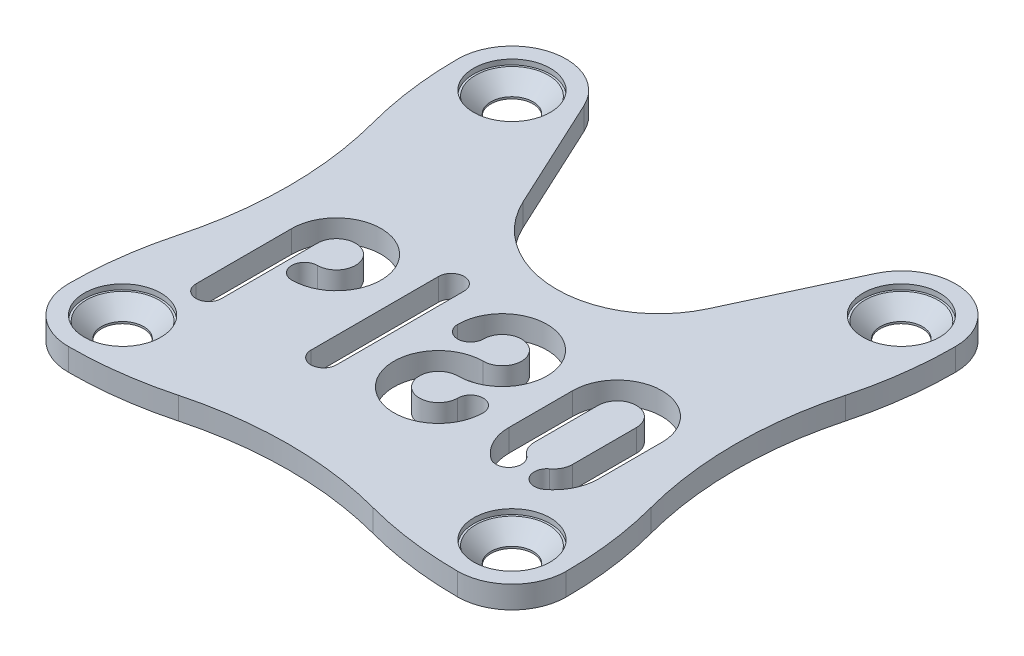
SolidWorks part; units mm, degrees
ref_plane "Front Plane" through (0, 0, 0) normal (0, 0, 1) x (1, 0, 0)
ref_plane "Top Plane" through (0, 0, 0) normal (0, 1, 0) x (1, 0, 0)
ref_plane "Right Plane" through (0, 0, 0) normal (1, 0, 0) x (0, 0, -1)
sketch "Sketch1" plane through (0, 0, 0) normal (0, 1, 0) x (1, 0, 0)
  line L0 (0, 19.5) -> (0, -19.5) construction
  line L1 (-19.5, 19.5) -> (19.5, 19.5)
  line L2 (-19.5, 19.5) -> (-19.5, -19.5)
  line L3 (-19.5, -19.5) -> (19.5, -19.5)
  line L4 (19.5, 19.5) -> (19.5, -19.5)
  line L5 (-19.5, 19.5) -> (19.5, -19.5) construction
  line L6 (-19.5, -19.5) -> (19.5, 19.5) construction
  line L7 (-19.5, 35.2) -> (-19.5, -19.5) construction
  circle A0 centre (-15.25, 15.25) radius 1.65
  circle A1 centre (15.25, 15.25) radius 1.65
  circle A2 centre (-15.25, -15.25) radius 1.65
  circle A3 centre (15.25, -15.25) radius 1.65
  circle A4 centre (15.25, 15.25) radius 1.65 construction
  circle A5 centre (15.25, -15.25) radius 1.65 construction
  circle A6 centre (-15.25, -15.25) radius 1.65 construction
  circle A7 centre (-15.25, 15.25) radius 1.65 construction
  point P0 (0, 0)
extrude "Shape" add sketch "Sketch1" along normal blind 1.75
sketch "Sketch2" plane through (0, 1.75, 0) normal (0, 1, 0) x (1, 0, 0)
  line L0 (0, 19.5) -> (0, -19.5) construction
  line L2 (-15.25, 16.9) -> (-15.25, -16.9) construction
  line L3 (-15.25, 0) -> (-19.5, 0) construction
  line L4 (-19.5, 19.5) -> (-19.5, -19.5) construction
  line L5 (19.5, 19.5) -> (-19.5, 19.5) construction
  line L6 (-19.5, -19.5) -> (19.5, -19.5) construction
  line L7 (-15.25, 0) -> (-11, 0) construction
  line L8 (-7.2551, 8.1291) -> (-12.5383, 19.5)
  line L9 (7.2551, 8.1291) -> (12.5383, 19.5)
  line L10 (-12.5383, 19.5) -> (12.5383, 19.5)
  line L14 (19.5, -19.5) -> (19.5, 19.5)
  line L15 (19.5, 19.5) -> (-19.5, 19.5)
  line L16 (-19.5, 19.5) -> (-19.5, -19.5)
  line L17 (-19.5, -19.5) -> (19.5, -19.5)
  line L18 (19.5, -19.5) -> (19.5, 19.5)
  line L19 (19.5, 19.5) -> (-19.5, 19.5)
  line L20 (-19.5, 19.5) -> (-19.5, -19.5)
  line L21 (-19.5, -19.5) -> (19.5, -19.5)
  circle A0 centre (0, 11.5) radius 8
  circle A1 centre (-15.25, 15.25) radius 1.65 construction
  circle A2 centre (-15.25, -15.25) radius 1.65 construction
  circle A3 centre (-15.25, 15.25) radius 4.25
  circle A4 centre (15.25, 15.25) radius 4.25
  circle A5 centre (-15.25, -15.25) radius 4.25
  circle A6 centre (15.25, -15.25) radius 4.25
  line M3 (19.5, -19.5) -> (19.5, 19.5)
  line M4 (19.5, 19.5) -> (-19.5, 19.5)
  line M5 (-19.5, 19.5) -> (-19.5, -19.5)
  line M6 (-19.5, -19.5) -> (19.5, -19.5)
  dimension "D1" = 16
  dimension "D2" = 0
extrude "Camera cut" cut sketch "Sketch2" against normal up to next contours A0 L10 L8 | A0 | A0 L9 M4 | A3 L8 M4 | A4 L9 M4 | A3 L19 M5 | A4 L18 M4 | A6 M6 M3 | A5 M5 M6 region at (0, 1.75, -11.5) region at (-8.2479, 1.75, -16.7625) region at (-12.8704, 1.75, -18.9795) region at (8.2479, 1.75, -16.7625) region at (-18.5507, 1.75, -18.5507) region at (12.8704, 1.75, -18.9795) region at (18.5507, 1.75, -18.5507) region at (-18.5507, 1.75, 18.5507) region at (18.5507, 1.75, 18.5507)
sketch "Sketch4" plane through (0, 1.75, 0) normal (0, 1, 0) x (1, 0, 0)
  circle A0 centre (-15.25, 15.25) radius 3
  circle A1 centre (15.25, 15.25) radius 3
  circle A2 centre (15.25, -15.25) radius 3
  circle A3 centre (-15.25, -15.25) radius 3
  dimension "D1" = 6
extrude "Screw head cuts" cut sketch "Sketch4" against normal blind 0.4
chamfer "Screw head chamfers" distance 1.2 angle 45 4 edges at (-15.25, 1.35, 16.9) (15.25, 1.35, 16.9) (15.25, 1.35, -13.6) (-15.25, 1.35, -13.6)
sketch "Sketch5" plane through (0, 1.75, 0) normal (0, 1, 0) x (1, 0, 0)
  line L0 (-19.5, 15.25) -> (19.5, 15.25) construction
  line L1 (-19.5, -15.25) -> (19.5, -15.25) construction
  line L2 (0, -19.5) -> (0, 15.25) construction
  line L3 (-15.25, -19.5) -> (15.25, -19.5) construction
  line L4 (-17.5, 18.8556) -> (-17.5, -18.8556) construction
  line L5 (-19.5, 15.25) -> (-19.5, -15.25) construction
  line L6 (-17.5, 0) -> (0, 0) construction
  line L7 (-18.5, 17.9886) -> (-18.5, -17.9886) construction
  line L8 (-18.5, 0) -> (-17.5, 0) construction
  line L9 (-18.5, 0) -> (-19.5, 0) construction
  line L10 (-17.5, 0) -> (-19.5, 15.25) construction
  line L11 (-15.25, 15.25) -> (15.25, -15.25) construction
  line L12 (-18.5, 7.625) -> (-17.5, 7.625) construction
  line L13 (-19.5, 15.25) -> (-19.5, -15.25)
  line L14 (-15.25, -19.5) -> (15.25, -19.5)
  line L15 (19.5, -15.25) -> (19.5, 15.25)
  arc A0 (-19.5, -15.25) -> (-15.25, -19.5) centre (-15.25, -15.25) ccw construction
  arc A1 (-11.3957, 17.0408) -> (-19.5, 15.25) centre (-15.25, 15.25) ccw construction
  arc A2 (-19.5, 15.25) -> (-18.5, 7.625) centre (10.0703, 15.25) ccw
  arc A3 (-18.5, 7.625) -> (-18.5, -7.625) centre (-47.0703, 0) cw
  arc A4 (-19.5, -15.25) -> (-18.5, -7.625) centre (10.0703, -15.25) cw
  arc A5 (19.5, -15.25) -> (18.5, -7.625) centre (-10.0703, -15.25) ccw
  arc A6 (18.5, 7.625) -> (18.5, -7.625) centre (47.0703, 0) ccw
  arc A7 (19.5, 15.25) -> (18.5, 7.625) centre (-10.0703, 15.25) cw
  arc A8 (15.25, -19.5) -> (7.625, -18.5) centre (15.25, 10.0703) cw
  arc A9 (-7.625, -18.5) -> (7.625, -18.5) centre (0, -47.0703) cw
  arc A10 (-15.25, -19.5) -> (-7.625, -18.5) centre (-15.25, 10.0703) ccw
  dimension "D1" = 2
extrude "Beauty cuts" cut sketch "Sketch5" against normal up to next
sketch "Sketch9" plane through (0, 1.75, 0) normal (0, 1, 0) x (1, 0, 0)
  line L0 (-19.0742, -10.25) -> (19.0742, -10.25) construction
  line L1 (-13.5, -2.4579) -> (-13.5, -12.0246) construction
  line L2 (-17.5011, -0.25) -> (17.5011, -0.25) construction
  line L3 (-13.5, -10.25) -> (-13.5, -0.25) construction
  line L4 (-14.5, -10.25) -> (-14.5, -0.25)
  line L5 (-12.5, -10.25) -> (-12.5, -0.25)
  line L6 (-17.6282, -2.75) -> (17.6282, -2.75) construction
  line L7 (-13.5, 0.75) -> (-11, 0.75)
  line L8 (-14.5, -5.25) -> (-12.5, -5.25) construction
  line L9 (-11, -4.25) -> (-11, -6.25) construction
  line L10 (-4.5, 8.8583) -> (-4.5, -11.9643) construction
  line L11 (17.5011, -0.25) -> (17.5011, -10.25) construction
  line L12 (-17.9698, -5.25) -> (17.9698, -5.25) construction
  line L13 (-15.25, -15.25) -> (15.25, -15.25) construction
  line L14 (-4.5, -0.25) -> (-4.5, -10.25) construction
  line L15 (-3.5, -0.25) -> (-3.5, -10.25)
  line L16 (-5.5, -0.25) -> (-5.5, -10.25)
  line L17 (-5.5, -10.25) -> (-3.5, -10.25) construction
  line L18 (2, -2.4583) -> (2, -12.0116) construction
  line L19 (-17.5095, 0.75) -> (17.5095, 0.75) construction
  line L20 (-17.5264, -1.25) -> (17.5264, -1.25) construction
  line L21 (18.5331, -7.75) -> (-18.5331, -7.75) construction
  line L22 (0, 0.75) -> (0, -15.25) construction
  line L23 (11, 16.2381) -> (11, -30.4508) construction
  line L24 (7.5, -7.75) -> (7.5, -2.75)
  line L25 (14.5, -2.75) -> (14.5, -7.75)
  line L26 (-7.5, 0.75) -> (-7.5, -15.25) construction
  line L27 (-1.5, 0.75) -> (-1.5, -15.25) construction
  line L28 (5.5, 0.75) -> (5.5, -15.25) construction
  line L29 (-7.5, -7.25) -> (-5.5, -7.25) construction
  line L30 (-3.5, -5.25) -> (-1.5, -5.25) construction
  line L31 (5.5, -7.25) -> (7.5, -7.25) construction
  line L32 (-14.5, -10.25) -> (-14.5, -15.25) construction
  line L33 (14.5, -7.75) -> (14.5, -15.25) construction
  line L34 (-14.5, -12.75) -> (14.5, -12.75) construction
  line L35 (9.5, -2.75) -> (9.5, -7.75)
  line L36 (12.5, -2.75) -> (12.5, -7.75)
  arc A0 (-18.5, -7.625) -> (-18.5, 7.625) centre (-47.0703, 0) ccw construction
  arc A1 (18.5, 7.625) -> (18.5, -7.625) centre (47.0703, 0) ccw construction
  arc A2 (-14.5, -10.25) -> (-12.5, -10.25) centre (-13.5, -10.25) ccw
  arc A3 (-12.5, -0.25) -> (-14.5, -0.25) centre (-13.5, -0.25) ccw
  circle A4 centre (-11, -2.75) radius 3.5
  circle A5 centre (-11, -2.75) radius 1.5
  circle A6 centre (-11, -5.25) radius 1
  arc A7 (-18.5, -7.625) -> (-19.5, -15.25) centre (10.0703, -15.25) ccw construction
  arc A8 (19.5, -15.25) -> (18.5, -7.625) centre (-10.0703, -15.25) ccw construction
  arc A9 (-3.5, -0.25) -> (-5.5, -0.25) centre (-4.5, -0.25) ccw
  arc A10 (-5.5, -10.25) -> (-3.5, -10.25) centre (-4.5, -10.25) ccw
  circle A11 centre (2, -2.75) radius 3.5
  circle A12 centre (2, -2.75) radius 1.5
  circle A13 centre (2, -7.75) radius 3.5
  circle A14 centre (2, -7.75) radius 1.5
  circle A15 centre (-0.5, -2.75) radius 1
  circle A16 centre (4.5, -7.75) radius 1
  circle A17 centre (9.5, -9.75) radius 1
  circle A18 centre (12.5, -9.75) radius 1
  circle A19 centre (11, -2.75) radius 3.5
  circle A20 centre (11, -2.75) radius 1.5
  circle A21 centre (11, -7.75) radius 3.5
  circle A22 centre (11, -7.75) radius 1.5
  point P16 (-13.5, -5.25)
  point P23 (-13.5, -0.25)
  point P41 (17.5011, -5.25)
  point P47 (-4.5, -5.25)
  point P106 (0, -12.75)
  dimension "D1" = 3
  dimension "D2" = 10
  dimension "D3" = 2
  dimension "D4" = 2.5
  dimension "D5" = 5
sketch "Sketch6" plane through (0, 1.75, 0) normal (0, 1, 0) x (1, 0, 0)
  line L0 (-19.116, -10.5) -> (19.116, -10.5) construction
  arc A0 (-18.5, -7.625) -> (-19.5, -15.25) centre (10.0703, -15.25) ccw construction
  arc A1 (19.5, -15.25) -> (18.5, -7.625) centre (-10.0703, -15.25) ccw construction
  arc A2 (7.625, -18.5) -> (-7.625, -18.5) centre (0, -47.0703) ccw construction
  text T0 "P180" font "Arial Rounded MT Bold" height 11
  point P12 (0, -17.5)
  dimension "D1" = 7
extrude "Name cut" [suppressed] cut sketch "Sketch6" against normal up to next
sketch "Sketch7" [suppressed] plane through (0, 1.75, 0) normal (0, 1, 0) x (1, 0, 0)
  line L0 (-14.242, 0.0875) -> (-11.5479, 0.0875) construction
  line L1 (-13.5094, 0.0875) -> (-12.5094, 0.0875)
  line L2 (-13.5094, 0.0875) -> (-13.5094, -6.375)
  line L3 (-13.5094, -6.375) -> (-12.5094, -6.375)
  line L4 (-12.5094, 0.0875) -> (-12.5094, -6.375)
  line L5 (-11.5672, -6.375) -> (-13.5094, -6.375) construction
  line L6 (-13.5094, -1.5625) -> (-13.5094, -4.725) construction
  line L7 (4.4881, -4.175) -> (4.4602, -5.55) construction
  line L8 (12.3578, 0.225) -> (12.4287, -10.6375) construction
  line L9 (3.9671, 0.225) -> (4.9671, 0.225)
  line L10 (3.9671, 0.225) -> (3.9671, -10.6375)
  line L11 (3.9671, -10.6375) -> (4.9671, -10.6375)
  line L12 (4.9671, 0.225) -> (4.9671, -10.6375)
  line L13 (3.9671, 0.225) -> (4.9671, -10.6375) construction
  line L14 (3.9671, -10.6375) -> (4.9671, 0.225) construction
  line L16 (11.8933, 0.225) -> (12.8933, 0.225)
  line L17 (11.8933, 0.225) -> (11.8933, -10.6375)
  line L18 (11.8933, -10.6375) -> (12.8933, -10.6375)
  line L19 (12.8933, 0.225) -> (12.8933, -10.6375)
  line L20 (11.8933, 0.225) -> (12.8933, -10.6375) construction
  line L21 (11.8933, -10.6375) -> (12.8933, 0.225) construction
  point P14 (4.4671, -5.2063)
  point P19 (12.3933, -5.2063)
  dimension "D1" = 1
extrude "Name islands" [suppressed] add sketch "Sketch7" against normal up to surface (1.75 mm away) up to face at (0, 0, 1.5649)
fillet "Name fillets" [suppressed] radius 1
extrude "Name" cut sketch "Sketch9" against normal up to next contours A4 L4 A2 L5 | A3 A4 L5 | A6 A4 A3 L5 A5 | A6 | L16 A10 L15 A9 | A16 A14 A11 A13 | A16 | A13 A11 | A15 A12 A13 A11 | A15 | A19 A21 L35 A20 L36 | L24 A21 A19 | A21 A19 L35 | A17 A22 L35 A19 A21 | A19 A21 L25 | A21 L36 A19 | L36 A22 A18 A21 A19 | A18 | A17 region at (-13.5665, 1.75, 7.9877) region at (-13.327, 1.75, 2.7635) region at (-11.8449, 1.75, -0.5567) region at (-11, 1.75, 5.25) region at (-4.5, 1.75, 5.25) region at (7.805, 1.75, 5.25) region at (8.5511, 1.75, 7.5495) region at (11, 1.75, -0.6578) region at (9.1656, 1.75, 5.25) region at (9.5, 1.75, 9.75) region at (14.195, 1.75, 5.25) region at (12.5, 1.75, 9.75) region at (13.4489, 1.75, 7.5495) region at (12.8344, 1.75, 5.25) region at (5.1417, 1.75, 4.0702) region at (-0.5, 1.75, 2.75) region at (2, 1.75, 5.25) region at (0.6423, 1.75, 6.0757) region at (4.5, 1.75, 7.75)
